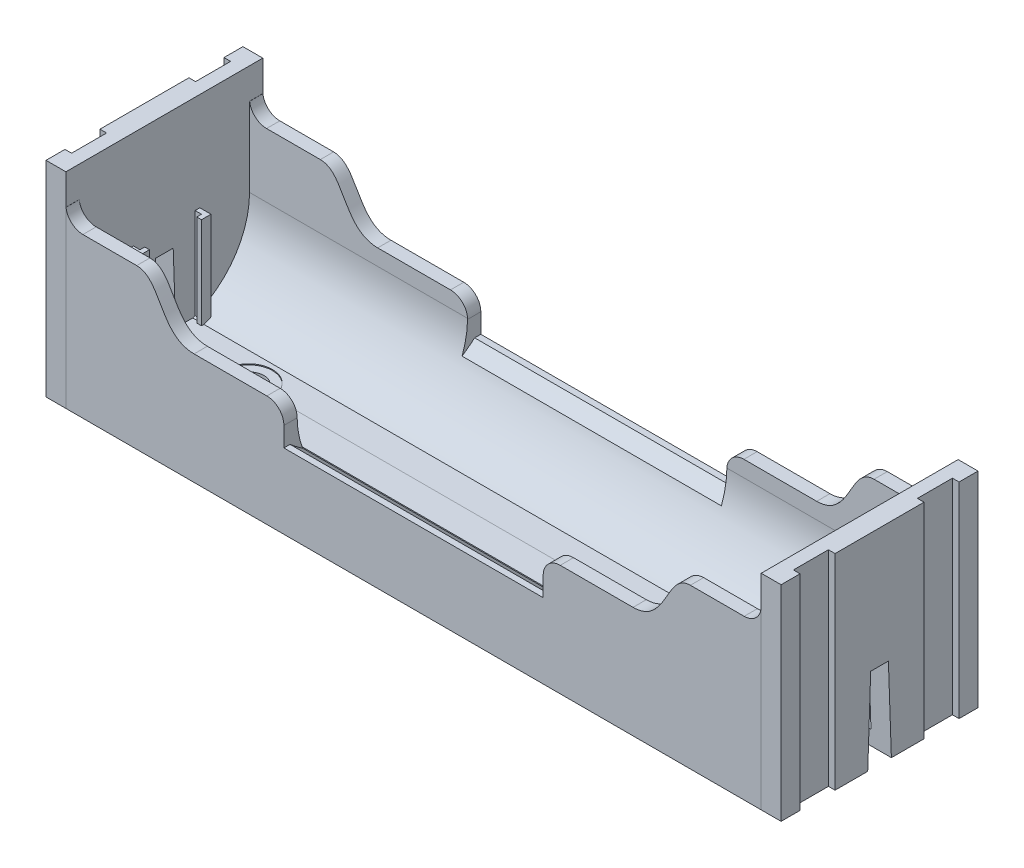
SolidWorks part; units mm, degrees
ref_plane "Спереди" through (0, 0, 0) normal (0, 0, 1) x (1, 0, 0)
ref_plane "Сверху" through (0, 0, 0) normal (0, 1, 0) x (1, 0, 0)
ref_plane "Справа" through (0, 0, 0) normal (1, 0, 0) x (0, 0, -1)
sketch "Эскиз1" plane through (0, 0, 0) normal (0, 0, 1) x (1, 0, 0)
  line L0 (-36.725, 0) -> (36.725, 0)
  line L1 (-36.725, 0) -> (-36.725, 18.61)
  line L2 (-36.725, 18.61) -> (-34.925, 18.61) construction
  line L3 (-34.925, 16.81) -> (-29.245, 16.81)
  line L4 (-23.185, 11.76) -> (-15.495, 11.76)
  line L5 (-15.495, 11.76) -> (-15.495, 9.96) construction
  line L6 (-13.695, 9.96) -> (-13.695, 7.9)
  line L7 (-13.695, 7.9) -> (13.695, 7.9)
  line L8 (0, 7.9) -> (0, 0) construction
  line L9 (36.725, 0) -> (36.725, 18.61)
  line L10 (34.925, 16.81) -> (29.245, 16.81)
  line L11 (23.185, 11.76) -> (15.495, 11.76)
  line L12 (13.695, 9.96) -> (13.695, 7.9)
  arc A0 (-36.725, 18.61) -> (-34.925, 16.81) centre (-34.925, 18.61) ccw
  arc A1 (-15.495, 11.76) -> (-13.695, 9.96) centre (-15.495, 9.96) cw
  arc A2 (36.725, 18.61) -> (34.925, 16.81) centre (34.925, 18.61) cw
  arc A3 (15.495, 11.76) -> (13.695, 9.96) centre (15.495, 9.96) ccw
  spline S0 degree 3 poles (-29.245, 16.81) (-26.6157, 16.7858) (-26.8128, 11.7896) (-23.185, 11.76) knots 0 0 0 0 1 1 1 1
  spline S1 degree 3 poles (29.245, 16.81) (26.6157, 16.7858) (26.8128, 11.7896) (23.185, 11.76) knots 0 0 0 0 1 1 1 1
  point P4 (0, 0)
  dimension "D1" = 73.45
  dimension "D2" = 18.61
  dimension "D3" = 1.8
  dimension "D4" = 5.68
  dimension "D5" = 7.69
  dimension "D6" = 5.05
  dimension "D7" = 6.06
  dimension "D8" = 1.8
  dimension "D9" = 2.06
extrude "Бобышка-Вытянуть1" add sketch "Эскиз1" against normal blind 10.4
sketch "Эскиз2" plane through (-36.725, 0, 0) normal (-1, 0, 0) x (0, 0, 1)
  line L5 (0, 18.61) -> (0, 0) construction
  line L42 (0, 1.5749) -> (-3, 1.5749)
  line L43 (-3, -0.9251) -> (-3, 1.5749) construction
  line L44 (-9, 10.0602) -> (-9, 18.4052)
  line L45 (-9, 18.4052) -> (-10.7657, 18.4052)
  line L46 (-10.7657, 18.4052) -> (-10.7657, 19.9735)
  line L47 (-10.7657, 19.9735) -> (0, 19.9735)
  line L48 (0, 19.9735) -> (0, 1.5749)
  arc A3 (-9, 10.0602) -> (-3, 1.5749) centre (0, 10.0602) ccw
  dimension "D1" = 3
  dimension "D3" = 9
  dimension "D2" = 2.5
  dimension "D5" = 3
extrude "Вырез-Вытянуть1" cut sketch "Эскиз2" against normal through all
sketch "Эскиз3" plane through (-36.725, 0, 0) normal (-1, 0, 0) x (0, 0, 1)
  line L0 (0, 0) -> (-10.4, 0) construction
  line L1 (0, 0) -> (0, 19.1837) construction
  line L3 (-10.4, 0) -> (-5.2, 0) construction
  circle A0 centre (0, 19.3) radius 15
  dimension "D1" = 19.3
extrude "Вырез-Вытянуть2" cut sketch "Эскиз3" against normal up to surface (50.42 mm away) from surface contours A0 up to face at (13.695, 8.9281, -9.649) starting at face at (-13.695, 8.9281, -9.649)
mirror "Зеркальное отражение6" about plane through (-34.925, 18.61, 0) normal (0, 0, 1) of bodies 103 125
sketch "Эскиз4" plane through (0, 0, 0) normal (0, -1, 0) x (1, 0, 0)
  line L0 (36.725, 0) -> (-36.725, 0) construction
  line L8 (-36.05, -3.25) -> (-36.05, -2.75) construction
  line L9 (36.05, 2.75) -> (36.05, 3.25) construction
  line L10 (36.05, -3.25) -> (36.05, -2.75) construction
  line L11 (36.725, -10.4) -> (36.725, 0) construction
  line L12 (-36.05, -3.25) -> (-37.25, -3.25)
  line L13 (-36.05, -3.25) -> (-36.05, -2.75)
  line L14 (-36.05, 3.25) -> (-37.25, 3.25)
  line L17 (36.05, 2.75) -> (36.05, 3.25)
  line L18 (-35.55, -3.75) -> (-35.55, -2.75)
  line L19 (-37.25, 3.75) -> (-35.55, 3.75)
  line L21 (-37.25, -3.75) -> (-35.55, -3.75)
  line L23 (37.25, -3.75) -> (37.25, -3.25)
  line L24 (35.55, -2.75) -> (36.05, -2.75)
  line L25 (-35.55, 3.75) -> (-35.55, 2.75)
  line L26 (-37.25, 3.25) -> (-37.25, 3.75)
  line L27 (-35.55, 2.75) -> (-36.05, 2.75)
  line L28 (-35.55, -2.75) -> (-36.05, -2.75)
  line L29 (-37.25, -3.75) -> (-37.25, -3.25)
  line L31 (-36.05, 2.75) -> (-36.05, 3.25)
  line L32 (-36.05, 2.75) -> (-36.05, 3.25) construction
  line L33 (35.55, 2.75) -> (36.05, 2.75)
  line L34 (37.25, 3.25) -> (37.25, 3.75)
  line L35 (35.55, 3.75) -> (35.55, 2.75)
  line L36 (37.25, -3.75) -> (35.55, -3.75)
  line L37 (37.25, 3.75) -> (35.55, 3.75)
  line L38 (35.55, -3.75) -> (35.55, -2.75)
  line L39 (36.05, 3.25) -> (37.25, 3.25)
  line L41 (36.05, -3.25) -> (37.25, -3.25)
  line L42 (36.05, -3.25) -> (36.05, -2.75)
  point P0 (35.8, 2.75)
  point P5 (0, 0)
  point P31 (0, 0)
  dimension "D1" = 5.5
  dimension "D2" = 72.1
  dimension "D3" = 0.5
  dimension "D4" = 0.5
  dimension "D5" = 2.75
  dimension "D6" = 0.5
  dimension "D7" = 0.5
  dimension "D8" = 0.675
sketch "Эскиз5" plane through (0, 0, 0) normal (0, -1, 0) x (1, 0, 0)
  line L0 (36.725, 10.4) -> (36.725, -10.4)
  line L5 (36.725, -10.4) -> (38.825, -10.4)
  line L6 (36.725, 10.4) -> (38.825, 10.4)
  line L12 (38.825, 10.4) -> (38.825, 8.4)
  line L14 (38.125, 8.4) -> (38.125, 4.7)
  line L15 (38.825, 4.7) -> (38.125, 4.7)
  line L16 (38.825, -4.7) -> (38.125, -4.7)
  line L17 (38.125, -8.4) -> (38.825, -8.4)
  line L18 (38.125, 8.4) -> (38.825, 8.4)
  line L20 (38.125, -4.7) -> (38.125, -8.4)
  line L21 (-38.125, 8.4) -> (-38.825, 8.4)
  line L22 (38.825, -8.4) -> (38.825, -10.4)
  line L23 (38.825, 4.7) -> (38.825, -4.7)
  line L24 (-38.825, 4.7) -> (-38.125, 4.7)
  line L25 (-38.825, -4.7) -> (-38.125, -4.7)
  line L26 (-38.125, -8.4) -> (-38.825, -8.4)
  line L27 (-38.825, -10.4) -> (-38.125, -10.4)
  line L28 (-36.725, -10.4) -> (-38.125, -10.4)
  line L29 (-38.825, -8.4) -> (-38.825, -10.4)
  line L30 (-38.125, -4.7) -> (-38.125, -8.4)
  line L31 (-38.825, 4.7) -> (-38.825, -4.7)
  line L32 (-38.125, 8.4) -> (-38.125, 4.7)
  line L33 (-38.825, 10.4) -> (-38.825, 8.4)
  line L34 (-36.725, 10.4) -> (-38.825, 10.4)
  line L35 (-36.725, 10.4) -> (-36.725, -10.4)
  point P4 (0, 0)
  point P12 (38.475, 0)
  point P15 (38.825, 0)
  dimension "D1" = 2.1
  dimension "D3" = 9.4
sketch "Эскиз17" [suppressed] plane through (0, 0, 0) normal (0, 0, 1) x (1, 0, 0)
  line L1 (-36.725, 1.5749) -> (36.725, 1.5749)
  line L2 (-36.725, 1.5749) -> (-36.725, 0)
  line L3 (-36.725, 0) -> (36.725, 0)
  line L4 (36.725, 1.5749) -> (36.725, 0)
  line L5 (-36.725, 1.5749) -> (36.725, 0) construction
  line L6 (-36.725, 0) -> (36.725, 1.5749) construction
  point P4 (0, 0.7875)
extrude "Бобышка-Вытянуть12" [suppressed] add sketch "Эскиз17" along normal blind 9.65
mirror "Зеркальное отражение7" [suppressed] of bodies 139
extrude "Бобышка-Вытянуть8" add sketch "Эскиз5" against normal blind 21.65
extrude "Бобышка-Вытянуть9" add sketch "Эскиз4" against normal blind 11.28
sketch "Эскиз16" plane through (0, 0, 0) normal (0, -1, 0) x (1, 0, 0)
  line L0 (-38.825, 0) -> (38.825, 0) construction
  line L5 (-36.05, 1.25) -> (-39.4409, 1.25)
  line L9 (-36.05, -1.25) -> (-36.05, 1.25)
  line L10 (-39.4409, 1.25) -> (-39.4409, -1.25)
  line L11 (-39.4409, -1.25) -> (-36.05, -1.25)
  line L12 (39.4409, 1.25) -> (39.4409, -1.25)
  line L13 (36.05, 1.25) -> (39.4409, 1.25)
  line L14 (36.05, -1.25) -> (36.05, 1.25)
  line L15 (39.4409, -1.25) -> (36.05, -1.25)
  line L16 (38.825, -4.7) -> (38.825, 4.7) construction
  line L18 (-38.825, 0) -> (38.825, 0) construction
  point P0 (0, 0)
  point P17 (0, 0)
  dimension "D1" = 2.5
  dimension "D2" = 72.1
  dimension "D3" = 3.3909
  dimension "D4" = 2.775
  dimension "D5" = 3.3909
  dimension "D6" = 2.5
sketch "Эскиз18" plane through (0, 0, 0) normal (0, -1, 0) x (1, 0, 0)
  line L0 (-27.81, 0) -> (27.81, 0) construction
  circle A0 centre (-27.81, 0) radius 1.6
  circle A1 centre (27.81, 0) radius 1.6
  point P4 (0, 0)
  dimension "D1" = 55.62
extrude "Вырез-Вытянуть5" cut sketch "Эскиз16" against normal blind 9 draft 2
extrude "Вырез-Вытянуть6" cut sketch "Эскиз18" against normal blind 9
sketch "Эскиз19" [suppressed] plane through (0, 0, 0) normal (0, -1, 0) x (1, 0, 0)
  line L0 (-27.81, 0) -> (27.81, 0) construction
  circle A0 centre (27.81, 0) radius 1.6
  circle A1 centre (-27.81, 0) radius 1.6
  point P4 (0, 0)
  point P7 (-27.81, 0)
  dimension "D1" = 55.62
extrude "Вырез-Вытянуть7" [suppressed] cut sketch "Эскиз19" against normal blind 9
sketch "Эскиз20" [suppressed] plane through (0, 1.5749, 0) normal (0, 1, 0) x (1, 0, 0)
  circle A0 centre (27.81, 0) radius 2.5
  circle A1 centre (-27.81, 0) radius 2.5
extrude "Вырез-Вытянуть8" [suppressed] cut sketch "Эскиз20" against normal blind 0.1
sketch "Эскиз21" plane through (0, 1.5749, 0) normal (0, 1, 0) x (1, 0, 0)
  circle A0 centre (27.81, 0) radius 2.5
  circle A1 centre (-27.81, 0) radius 2.5
extrude "Вырез-Вытянуть9" cut sketch "Эскиз21" against normal blind 0.1
sketch "Эскиз22" [suppressed] plane through (0, 0, 0) normal (0, -1, 0) x (-1, 0, 0)
  line L0 (-38.825, 0) -> (38.825, 0) construction
  line L5 (-36.05, 1.25) -> (-39.4409, 1.25)
  line L9 (-36.05, -1.25) -> (-36.05, 1.25)
  line L10 (-39.4409, 1.25) -> (-39.4409, -1.25)
  line L11 (-39.4409, -1.25) -> (-36.05, -1.25)
  line L12 (39.4409, 1.25) -> (39.4409, -1.25)
  line L13 (36.05, 1.25) -> (39.4409, 1.25)
  line L14 (36.05, -1.25) -> (36.05, 1.25)
  line L15 (39.4409, -1.25) -> (36.05, -1.25)
  line L16 (38.825, -4.7) -> (38.825, 4.7) construction
  line L18 (-38.825, 0) -> (38.825, 0) construction
  line L19 (-38.825, 4.7) -> (-38.825, -4.7) construction
  point P0 (0, 0)
  point P17 (0, 0)
  dimension "D1" = 2.5
  dimension "D2" = 72.1
  dimension "D3" = 3.3909
  dimension "D4" = 2.775
  dimension "D5" = 3.3909
  dimension "D6" = 2.5
  dimension "D7" = 2.775
extrude "Вырез-Вытянуть10" [suppressed] cut sketch "Эскиз22" against normal blind 9 draft 2
pattern_linear "Линейный массив1" [suppressed] count 4 spacing 19.3 of bodies 160
sketch "Эскиз13" plane through (0, 21.65, 0) normal (0, 1, 0) x (1, 0, 0)
  line L0 (-38.825, -9.4) -> (-36.725, -9.4) construction
  line L5 (-38.825, -10.4) -> (-38.825, -8.4) construction
  line L6 (-36.725, 10.4) -> (-36.725, -10.4) construction
  line L7 (38.125, -10.3058) -> (38.4945, -10.3058) construction
  line L9 (38.125, -9.0058) -> (38.4945, -9.0058) construction
  line L11 (38.4945, -9.0058) -> (-38.3934, -9.0058)
  line L12 (38.4945, -9.0058) -> (38.4945, -10.3058)
  line L13 (38.4945, -10.3058) -> (-38.3934, -10.3058)
  line L14 (-38.3934, -9.0058) -> (-38.3934, -10.3058)
  line L15 (38.4945, -9.0058) -> (-38.3934, -10.3058) construction
  line L16 (38.4945, -10.3058) -> (-38.3934, -9.0058) construction
  point P14 (0.0505, -9.6558)
extrude "Бобышка-Вытянуть10" [suppressed] add sketch "Эскиз13" against normal up to surface (10.7751 mm away) from offset 9.3 offset against normal yes
pattern_linear "Линейный массив2" [suppressed] count 2 spacing 19.3 of bodies 124
pattern_linear "Линейный массив3" [suppressed] count 3 spacing 19.3 of bodies 124
pattern_linear "Линейный массив4" [suppressed] count 2 spacing 19.3 of bodies 124
equation "\"D\"=0.8"
